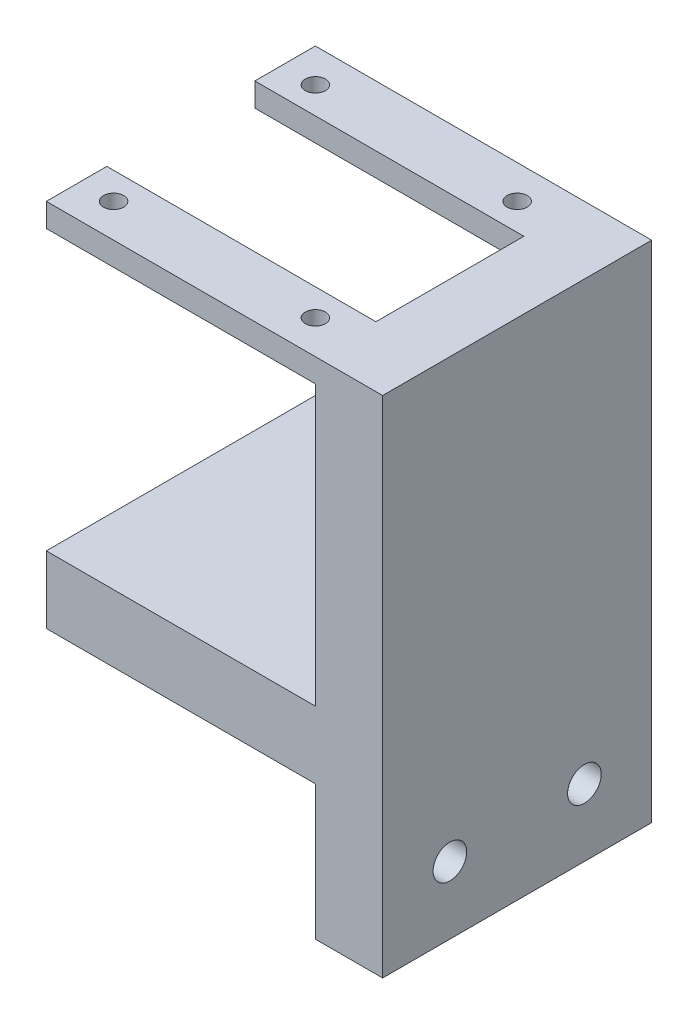
SolidWorks part; units mm, degrees
ref_plane "Front Plane" through (0, 0, 0) normal (0, 0, 1) x (1, 0, 0)
ref_plane "Top Plane" through (0, 0, 0) normal (0, 1, 0) x (1, 0, 0)
ref_plane "Right Plane" through (0, 0, 0) normal (1, 0, 0) x (0, 0, -1)
sketch "Sketch1" plane through (0, 0, 0) normal (1, 0, 0) x (0, 0, -1)
  line L0 (0, 27.5) -> (0, -27.5) construction
  line L5 (-20, 55) -> (20, 55)
  line L6 (-20, 55) -> (-20, 0)
  line L7 (-20, 0) -> (20, 0)
  line L8 (20, 55) -> (20, 0)
  line L9 (-20, 55) -> (20, 0) construction
  line L10 (-20, 0) -> (20, 55) construction
  line L11 (22, 0) -> (-22, 0) construction
  line L13 (-20, -20) -> (20, -20)
  line L14 (-20, -20) -> (-20, 0)
  line L15 (-20, 0) -> (20, 0)
  line L16 (20, -20) -> (20, 0)
  line L17 (-20, -20) -> (20, 0) construction
  line L18 (-20, 0) -> (20, -20) construction
  line L19 (10, -15) -> (-10, -15) construction
  line L20 (10, -15) -> (10, -5) construction
  line L21 (10, -5) -> (-10, -5) construction
  line L22 (-10, -15) -> (-10, -5) construction
  line L23 (10, -15) -> (-10, -5) construction
  line L24 (10, -5) -> (-10, -15) construction
  circle A0 centre (-10, -10) radius 2.5
  circle A1 centre (10, -10) radius 2.5
  point P1 (0, 27.5)
  point P10 (0, -10)
  point P11 (0, -10)
  dimension "D5" = 5
  dimension "D1" = 55
  dimension "D2" = 40
  dimension "D3" = 20
  dimension "D4" = 20
extrude "Boss-Extrude1" add sketch "Sketch1" along normal blind 10 contours L8 L5 L6 L7 | L13 L16 L7 L14 A1 A0 region at (0, 27.5, 0) region at (0, -10, 0)
sketch "Sketch3" plane through (0, 0, 0) normal (-1, 0, 0) x (0, 0, 1)
  line L0 (20, 55) -> (20, -20) construction
  line L1 (-20, 10) -> (20, 10)
  line L2 (-20, 10) -> (-20, 0)
  line L3 (-20, 0) -> (20, 0)
  line L4 (20, 10) -> (20, 0)
  line L5 (-20, 10) -> (20, 0) construction
  line L6 (-20, 0) -> (20, 10) construction
  dimension "D1" = 10
extrude "Boss-Extrude2" add sketch "Sketch3" along normal blind 40
sketch "Sketch4" plane through (0, 0, 0) normal (-1, 0, 0) x (0, 0, 1)
  line L13 (-20, 55) -> (-11, 55)
  line L14 (-20, 55) -> (-20, 51.5)
  line L15 (-20, 51.5) -> (-11, 51.5)
  line L16 (-11, 55) -> (-11, 51.5)
  dimension "D1" = 9
  dimension "D2" = 3.5
extrude "Boss-Extrude3" add sketch "Sketch4" along normal blind 40
sketch "Sketch5" plane through (0, 55, 0) normal (0, 1, 0) x (1, 0, 0)
  line L1 (-40, 20) -> (-35, 20) construction
  line L2 (-40, 20) -> (-40, 15) construction
  line L3 (-40, 15) -> (-35, 15) construction
  line L4 (-35, 20) -> (-35, 15) construction
  line L5 (10, 20) -> (-40, 20) construction
  line L7 (0, 20) -> (-5, 20) construction
  line L8 (0, 20) -> (0, 15) construction
  line L9 (0, 15) -> (-5, 15) construction
  line L10 (-5, 20) -> (-5, 15) construction
  circle A0 centre (-35, 15) radius 1.5
  circle A1 centre (-5, 15) radius 1.5
  dimension "D3" = 3
  dimension "D7" = 3
  dimension "D1" = 5
  dimension "D2" = 5
  dimension "D4" = 5
  dimension "D5" = 5
  dimension "D6" = 30
extrude "Cut-Extrude1" cut sketch "Sketch5" against normal up to next
mirror "Mirror2" about plane through (0, 0, 0) normal (0, 0, 1) of "Cut-Extrude1", "Boss-Extrude3"
